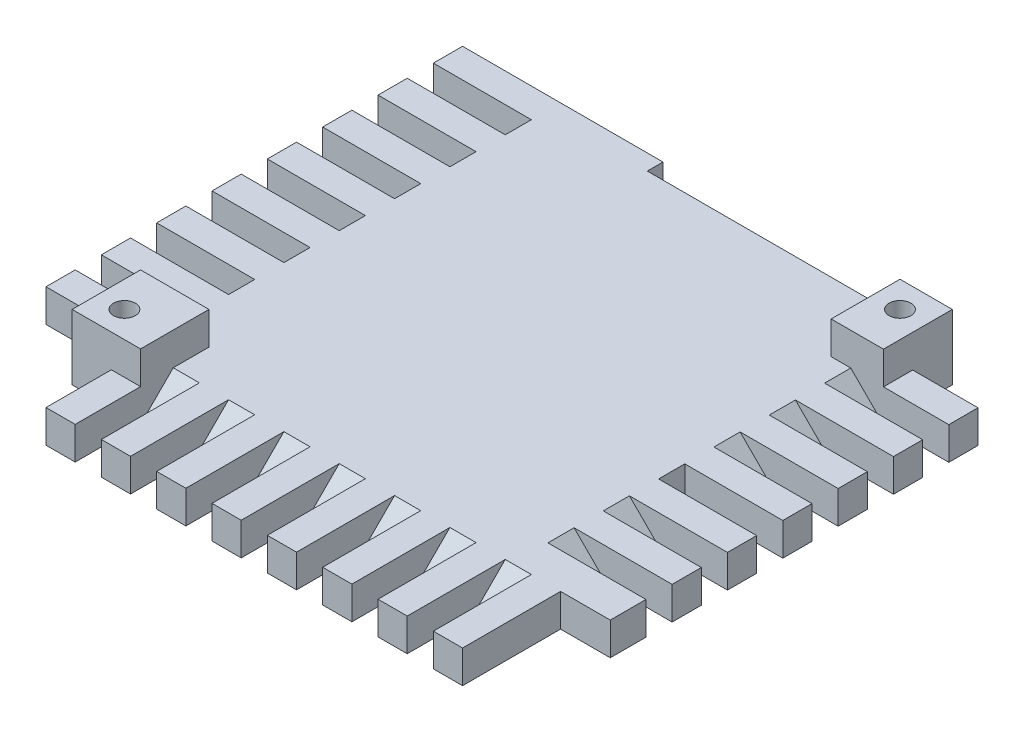
SolidWorks part; units mm, degrees
ref_plane "Front Plane" through (0, 0, 0) normal (0, 0, 1) x (1, 0, 0)
ref_plane "Top Plane" through (0, 0, 0) normal (0, 1, 0) x (1, 0, 0)
ref_plane "Right Plane" through (0, 0, 0) normal (1, 0, 0) x (0, 0, -1)
sketch "Base outline" plane through (0, 0, 0) normal (0, 1, 0) x (1, 0, 0)
  line L0 (3.74, 1.5) -> (3.74, 0) construction
  line L1 (6.2016, 20.2) -> (20.2, 20.2)
  line L4 (20.2, 20.2) -> (20.2, 18.38)
  line L6 (3.14, 0) -> (3.14, 1.5)
  line L7 (3.14, 1.5) -> (4.34, 1.5)
  line L8 (4.34, 0) -> (4.34, 1.5)
  line L10 (5.68, 0) -> (5.68, 1.5)
  line L11 (5.68, 1.5) -> (6.88, 1.5)
  line L12 (6.88, 0) -> (6.88, 1.5)
  line L13 (8.22, 0) -> (8.22, 1.5)
  line L14 (8.22, 1.5) -> (9.42, 1.5)
  line L15 (9.42, 0) -> (9.42, 1.5)
  line L16 (10.76, 0) -> (10.76, 1.5)
  line L17 (10.76, 1.5) -> (11.96, 1.5)
  line L18 (11.96, 0) -> (11.96, 1.5)
  line L19 (13.3, 0) -> (13.3, 1.5)
  line L20 (13.3, 1.5) -> (14.5, 1.5)
  line L21 (14.5, 0) -> (14.5, 1.5)
  line L22 (15.84, 0) -> (15.84, 1.5)
  line L23 (15.84, 1.5) -> (17.04, 1.5)
  line L24 (17.04, 0) -> (17.04, 1.5)
  line L25 (18.38, 0) -> (18.38, 1.5)
  line L26 (18.38, 1.5) -> (19.58, 1.5)
  line L27 (19.58, 0) -> (19.58, 1.5)
  line L28 (3.14, 0) -> (4.34, 0) construction
  line L35 (8.22, 0) -> (8.22, -3)
  line L37 (4.34, 0) -> (4.34, -3)
  line L38 (4.34, -3) -> (5.68, -3)
  line L39 (5.68, 0) -> (5.68, -3)
  line L40 (6.88, -3) -> (8.22, -3)
  line L41 (6.88, 0) -> (6.88, -3)
  line L42 (10.76, 0) -> (10.76, -3)
  line L43 (9.42, -3) -> (10.76, -3)
  line L44 (9.42, 0) -> (9.42, -3)
  line L45 (13.3, 0) -> (13.3, -3)
  line L46 (11.96, -3) -> (13.3, -3)
  line L47 (11.96, 0) -> (11.96, -3)
  line L48 (15.84, 0) -> (15.84, -3)
  line L49 (14.5, -3) -> (15.84, -3)
  line L50 (14.5, 0) -> (14.5, -3)
  line L51 (18.38, 0) -> (18.38, -3)
  line L52 (17.04, -3) -> (18.38, -3)
  line L53 (17.04, 0) -> (17.04, -3)
  line L54 (5.68, 0) -> (6.88, 0) construction
  line L55 (1.5, 3.74) -> (0, 3.74) construction
  line L56 (0, 3.14) -> (1.5, 3.14)
  line L58 (0, 4.34) -> (1.5, 4.34)
  line L59 (1.5, 3.14) -> (1.5, 4.34)
  line L61 (0, 6.88) -> (1.5, 6.88)
  line L62 (1.5, 5.68) -> (1.5, 6.88)
  line L63 (0, 5.68) -> (1.5, 5.68)
  line L64 (0, 9.42) -> (1.5, 9.42)
  line L65 (1.5, 8.22) -> (1.5, 9.42)
  line L66 (0, 8.22) -> (1.5, 8.22)
  line L67 (0, 11.96) -> (1.5, 11.96)
  line L68 (1.5, 10.76) -> (1.5, 11.96)
  line L69 (0, 10.76) -> (1.5, 10.76)
  line L70 (0, 14.5) -> (1.5, 14.5)
  line L71 (1.5, 13.3) -> (1.5, 14.5)
  line L72 (0, 13.3) -> (1.5, 13.3)
  line L73 (0, 17.04) -> (1.5, 17.04)
  line L74 (1.5, 15.84) -> (1.5, 17.04)
  line L75 (0, 15.84) -> (1.5, 15.84)
  line L76 (0, 19.58) -> (1.5, 19.58)
  line L77 (1.5, 18.38) -> (1.5, 19.58)
  line L78 (0, 18.38) -> (1.5, 18.38)
  line L79 (0, 6.88) -> (-3, 6.88)
  line L86 (-3, 6.88) -> (-3, 8.22)
  line L87 (0, 4.34) -> (-3, 4.34)
  line L89 (0, 5.68) -> (-3, 5.68)
  line L90 (-3, 4.34) -> (-3, 5.68)
  line L91 (0, 8.22) -> (-3, 8.22)
  line L92 (0, 9.42) -> (-3, 9.42)
  line L93 (-3, 9.42) -> (-3, 10.76)
  line L94 (0, 10.76) -> (-3, 10.76)
  line L95 (0, 11.96) -> (-3, 11.96)
  line L96 (-3, 11.96) -> (-3, 13.3)
  line L97 (0, 13.3) -> (-3, 13.3)
  line L98 (0, 14.5) -> (-3, 14.5)
  line L99 (-3, 14.5) -> (-3, 15.84)
  line L100 (0, 15.84) -> (-3, 15.84)
  line L101 (0, 17.04) -> (-3, 17.04)
  line L102 (-3, 17.04) -> (-3, 18.38)
  line L103 (0, 18.38) -> (-3, 18.38)
  line L104 (0, 4.34) -> (0, 6.88) construction
  line L105 (18.7, 3.74) -> (20.2, 3.74) construction
  line L106 (20.2, 4.34) -> (18.7, 4.34)
  line L108 (20.2, 3.14) -> (18.7, 3.14)
  line L109 (18.7, 4.34) -> (18.7, 3.14)
  line L111 (20.2, 6.88) -> (18.7, 6.88)
  line L112 (18.7, 6.88) -> (18.7, 5.68)
  line L113 (20.2, 5.68) -> (18.7, 5.68)
  line L114 (20.2, 9.42) -> (18.7, 9.42)
  line L115 (18.7, 9.42) -> (18.7, 8.22)
  line L116 (20.2, 8.22) -> (18.7, 8.22)
  line L117 (20.2, 11.96) -> (18.7, 11.96)
  line L118 (18.7, 11.96) -> (18.7, 10.76)
  line L119 (20.2, 10.76) -> (18.7, 10.76)
  line L120 (20.2, 14.5) -> (18.7, 14.5)
  line L121 (18.7, 14.5) -> (18.7, 13.3)
  line L122 (20.2, 13.3) -> (18.7, 13.3)
  line L123 (20.2, 17.04) -> (18.7, 17.04)
  line L124 (18.7, 17.04) -> (18.7, 15.84)
  line L125 (20.2, 15.84) -> (18.7, 15.84)
  line L129 (20.2, 8.22) -> (23.2, 8.22)
  line L135 (23.2, 8.22) -> (23.2, 6.88)
  line L136 (20.2, 5.68) -> (23.2, 5.68)
  line L138 (20.2, 4.34) -> (23.2, 4.34)
  line L139 (23.2, 5.68) -> (23.2, 4.34)
  line L140 (20.2, 6.88) -> (23.2, 6.88)
  line L141 (20.2, 10.76) -> (23.2, 10.76)
  line L142 (23.2, 10.76) -> (23.2, 9.42)
  line L143 (20.2, 9.42) -> (23.2, 9.42)
  line L144 (20.2, 13.3) -> (23.2, 13.3)
  line L145 (23.2, 13.3) -> (23.2, 11.96)
  line L146 (20.2, 11.96) -> (23.2, 11.96)
  line L147 (20.2, 15.84) -> (23.2, 15.84)
  line L148 (23.2, 15.84) -> (23.2, 14.5)
  line L149 (20.2, 14.5) -> (23.2, 14.5)
  line L150 (19.58, 0) -> (19.58, -3)
  line L151 (20.2, 3.14) -> (23.2, 3.14)
  line L153 (20.2, 5.68) -> (20.2, 6.88) construction
  line L155 (23.2, 3.14) -> (23.2, 1.5)
  line L156 (19.58, -3) -> (20.92, -3)
  line L158 (19.58, 0) -> (20.2, 0) construction
  line L159 (20.2, 0) -> (20.2, 3.14) construction
  line L160 (0, 3.14) -> (-3, 3.14)
  line L163 (23.2, 1.5) -> (20.92, 1.5)
  line L164 (20.92, -3) -> (20.92, 1.5)
  line L165 (-3, 3.14) -> (-3, 1.8)
  line L166 (1.8, -3) -> (3.14, -3)
  line L167 (3.14, -3) -> (3.14, 0)
  line L168 (0, 3.14) -> (0, 0) construction
  line L169 (0, 0) -> (3.14, 0) construction
  line L170 (0, 19.58) -> (-3, 19.58)
  line L171 (-3, 1.8) -> (0, 1.8)
  line L174 (0, 1.8) -> (0, 0)
  line L177 (0, 0) -> (1.8, 0)
  line L178 (1.8, -3) -> (1.8, 0)
  line L179 (-3, 19.58) -> (-3, 20.92)
  line L180 (-3, 20.92) -> (6.2016, 20.92)
  line L181 (6.2016, 20.92) -> (6.2016, 20.2)
  line L183 (20.2, 17.04) -> (23.2, 17.04)
  line L185 (20.2, 18.38) -> (23.2, 18.38)
  line L186 (23.2, 17.04) -> (23.2, 18.38)
  line L187 (20.2, 18.38) -> (18.7, 18.38) [skipped]
  line L188 (20.2, 19.58) -> (18.7, 19.58) [skipped]
  line L189 (18.7, 19.4) -> (18.7, 18.6) [skipped]
  circle A0 centre (1.2, 1.2) radius 0.5
  circle A1 centre (19, 19) radius 0.5
  dimension "D5" = 1
  dimension "D6" = 1
  dimension "D3" = 1.2
  dimension "D4" = 1.2
  dimension "D7" = 1.2
  dimension "D8" = 1.2
  dimension "D9" = 3.74
  dimension "D10" = 1.5
  dimension "D11" = 1.2
  dimension "D13" = 6
  dimension "D14" = 3
  dimension "D15" = 2.54
  dimension "D16" = 3.74
  dimension "D17" = 7
  dimension "D18" = 6
  dimension "D19" = 2.54
  dimension "D21" = 5
  dimension "D22" = 2.54
  dimension "D23" = 20.2
  dimension "D24" = 20.2
  dimension "D25" = 4.7016
  dimension "D12" = 7
  dimension "D20" = 7
extrude "Boss-Extrude1" add sketch "Base outline" along normal blind 1.5 contours L183 L186 L185 L4 L1 L181 L180 L179 L170 L76 L77 L78 L103 L102 L101 L73 L74 L75 L100 L99 L98 L70 L71 L72 L97 L96 L95 L67 L68 L69 L94 L93 L92 L64 L65 L66 L91 L86 L79 L61 L62 L63 L89 L90 L87 L58 L59 L56 L160 L165 L171 region at (10.0687, 0, -9.6701)
draft "Draft2" type of draft neutral plane draft angle 45 faces to draft 19 face at (1.5, 0.75, -18.98) face at (1.5, 0.75, -16.44) face at (1.5, 0.75, -13.9) face at (1.5, 0.75, -11.36) face at (1.5, 0.75, -8.82) face at (1.5, 0.75, -6.28) face at (1.5, 0.75, -3.74) face at (18.7, 0.75, -16.44) face at (18.7, 0.75, -13.9) face at (18.7, 0.75, -11.36) face at (18.7, 0.75, -6.28) face at (18.7, 0.75, -3.74) face at (18.98, 0.75, -1.5) face at (16.44, 0.75, -1.5) face at (13.9, 0.75, -1.5) face at (11.36, 0.75, -1.5) face at (8.82, 0.75, -1.5) face at (6.28, 0.75, -1.5) face at (3.74, 0.75, -1.5) neutral plane through (0, 1.5, 0) neutral plane normal (0, 1, 0) parameters "D1"=45
sketch "Spacer outline" plane through (0, 1.5, 0) normal (0, 1, 0) x (1, 0, 0)
  line L0 (0, 1.8) -> (0, 3.14)
  line L1 (-3, 3.14) -> (1.5, 3.14) construction
  line L2 (0, 3.14) -> (1.5, 3.14)
  line L3 (1.5, 3.14) -> (3.14, 3.14)
  line L4 (3.14, 3.14) -> (3.14, 1.5)
  line L5 (1.8, 0) -> (3.14, 0)
  line L6 (3.14, -3) -> (3.14, 1.5) construction
  line L7 (18.7, 17.04) -> (17.8, 17.04)
  line L8 (17.8, 17.04) -> (17.8, 20.2)
  line L9 (6.2016, 20.2) -> (20.2, 20.2) construction
  line L10 (20.2, 20.2) -> (20.2, 18.38) construction
  line L11 (20.2, 18.38) -> (20.2, 17.04)
  line L12 (18.7, 17.04) -> (23.2, 17.04) construction
  line L13 (0, 1.8) -> (0, 0)
  line L14 (0, 0) -> (1.8, 0)
  line L15 (3.14, 0) -> (3.14, 1.5)
  line L16 (20.2, 17.04) -> (18.7, 17.04)
  line L17 (17.8, 20.2) -> (20.2, 20.2)
  line L18 (20.2, 20.2) -> (20.2, 18.38)
  dimension "D1" = 2.4
extrude "Boss-Extrude2" add sketch "Spacer outline" along normal blind 1.5
extrude "Cut-Extrude1" cut sketch "Sketch1<3>" along normal blind 5.5 contours A0 | A1
sketch "Sketch1<3>" plane through (0, 0, 0) normal (0, 1, 0) x (1, 0, 0) same geometry as "Base outline"
sketch "PCB outline" plane through (0, 3, 0) normal (0, 1, 0) x (1, 0, 0)
  line L3 (3.74, 1.2) -> (6.28, 1.2) construction
  line L4 (0, 0) -> (20.2, 0) construction
  line L5 (0, 0) -> (0, 20.2) construction
  line L6 (0, 20.2) -> (20.2, 20.2) construction
  line L7 (20.2, 0) -> (20.2, 20.2) construction
  line L8 (18.98, 1.2) -> (18.98, 3.74) construction
  line L9 (1.2, 3.74) -> (1.2, 6.28) construction
  circle A0 centre (3.74, 1.2) radius 0.6 construction
  circle A1 centre (6.28, 1.2) radius 0.6 construction
  circle A2 centre (8.82, 1.2) radius 0.6 construction
  circle A3 centre (11.36, 1.2) radius 0.6 construction
  circle A4 centre (13.9, 1.2) radius 0.6 construction
  circle A5 centre (16.44, 1.2) radius 0.6 construction
  circle A6 centre (18.98, 1.2) radius 0.6 construction
  circle A7 centre (18.98, 3.74) radius 0.6 construction
  circle A8 centre (18.98, 6.28) radius 0.6 construction
  circle A9 centre (18.98, 8.82) radius 0.6 construction
  circle A10 centre (18.98, 11.36) radius 0.6 construction
  circle A11 centre (18.98, 13.9) radius 0.6 construction
  circle A12 centre (18.98, 16.44) radius 0.6 construction
  circle A13 centre (1.2, 3.74) radius 0.5 construction
  circle A14 centre (1.2, 6.28) radius 0.5 construction
  circle A15 centre (1.2, 8.82) radius 0.5 construction
  circle A16 centre (1.2, 11.36) radius 0.5 construction
  circle A17 centre (1.2, 13.9) radius 0.5 construction
  circle A18 centre (1.2, 16.44) radius 0.5 construction
  circle A19 centre (1.2, 18.98) radius 0.5 construction
  dimension "D1" = 1.2
  dimension "D8" = 1
  dimension "D2" = 1.2
  dimension "D3" = 3.74
  dimension "D5" = 2.54
  dimension "D7" = 2.54
  dimension "D9" = 1.2
  dimension "D10" = 3.74
  dimension "D12" = 2.54
  dimension "D4" = 7
  dimension "D6" = 7
  dimension "D11" = 7
sketch "Sketch3" plane through (0, 1.5, 0) normal (0, 1, 0) x (1, 0, 0)
  line L0 (3.74, 1.5) -> (3.74, 0) construction
  line L1 (6.2016, 20.2) -> (20.2, 20.2)
  line L4 (20.2, 20.2) -> (20.2, 18.38)
  line L6 (3.14, 0) -> (3.14, 1.5)
  line L7 (3.14, 1.5) -> (4.34, 1.5)
  line L8 (4.34, 0) -> (4.34, 1.5)
  line L10 (5.68, 0) -> (5.68, 1.5)
  line L11 (5.68, 1.5) -> (6.88, 1.5)
  line L12 (6.88, 0) -> (6.88, 1.5)
  line L13 (8.22, 0) -> (8.22, 1.5)
  line L14 (8.22, 1.5) -> (9.42, 1.5)
  line L15 (9.42, 0) -> (9.42, 1.5)
  line L16 (10.76, 0) -> (10.76, 1.5)
  line L17 (10.76, 1.5) -> (11.96, 1.5)
  line L18 (11.96, 0) -> (11.96, 1.5)
  line L19 (13.3, 0) -> (13.3, 1.5)
  line L20 (13.3, 1.5) -> (14.5, 1.5)
  line L21 (14.5, 0) -> (14.5, 1.5)
  line L22 (15.84, 0) -> (15.84, 1.5)
  line L23 (15.84, 1.5) -> (17.04, 1.5)
  line L24 (17.04, 0) -> (17.04, 1.5)
  line L25 (18.38, 0) -> (18.38, 1.5)
  line L26 (18.38, 1.5) -> (19.58, 1.5)
  line L27 (19.58, 0) -> (19.58, 1.5)
  line L28 (3.14, 0) -> (4.34, 0) construction
  line L35 (8.22, 0) -> (8.22, -3)
  line L37 (4.34, 0) -> (4.34, -3)
  line L38 (4.34, -3) -> (5.68, -3)
  line L39 (5.68, 0) -> (5.68, -3)
  line L40 (6.88, -3) -> (8.22, -3)
  line L41 (6.88, 0) -> (6.88, -3)
  line L42 (10.76, 0) -> (10.76, -3)
  line L43 (9.42, -3) -> (10.76, -3)
  line L44 (9.42, 0) -> (9.42, -3)
  line L45 (13.3, 0) -> (13.3, -3)
  line L46 (11.96, -3) -> (13.3, -3)
  line L47 (11.96, 0) -> (11.96, -3)
  line L48 (15.84, 0) -> (15.84, -3)
  line L49 (14.5, -3) -> (15.84, -3)
  line L50 (14.5, 0) -> (14.5, -3)
  line L51 (18.38, 0) -> (18.38, -3)
  line L52 (17.04, -3) -> (18.38, -3)
  line L53 (17.04, 0) -> (17.04, -3)
  line L54 (5.68, 0) -> (6.88, 0) construction
  line L55 (1.5, 3.74) -> (0, 3.74) construction
  line L56 (0, 3.14) -> (1.5, 3.14)
  line L58 (0, 4.34) -> (1.5, 4.34)
  line L59 (1.5, 3.14) -> (1.5, 4.34)
  line L61 (0, 6.88) -> (1.5, 6.88)
  line L62 (1.5, 5.68) -> (1.5, 6.88)
  line L63 (0, 5.68) -> (1.5, 5.68)
  line L64 (0, 9.42) -> (1.5, 9.42)
  line L65 (1.5, 8.22) -> (1.5, 9.42)
  line L66 (0, 8.22) -> (1.5, 8.22)
  line L67 (0, 11.96) -> (1.5, 11.96)
  line L68 (1.5, 10.76) -> (1.5, 11.96)
  line L69 (0, 10.76) -> (1.5, 10.76)
  line L70 (0, 14.5) -> (1.5, 14.5)
  line L71 (1.5, 13.3) -> (1.5, 14.5)
  line L72 (0, 13.3) -> (1.5, 13.3)
  line L73 (0, 17.04) -> (1.5, 17.04)
  line L74 (1.5, 15.84) -> (1.5, 17.04)
  line L75 (0, 15.84) -> (1.5, 15.84)
  line L76 (0, 19.58) -> (1.5, 19.58)
  line L77 (1.5, 18.38) -> (1.5, 19.58)
  line L78 (0, 18.38) -> (1.5, 18.38)
  line L79 (0, 6.88) -> (-3, 6.88)
  line L86 (-3, 6.88) -> (-3, 8.22)
  line L87 (0, 4.34) -> (-3, 4.34)
  line L89 (0, 5.68) -> (-3, 5.68)
  line L90 (-3, 4.34) -> (-3, 5.68)
  line L91 (0, 8.22) -> (-3, 8.22)
  line L92 (0, 9.42) -> (-3, 9.42)
  line L93 (-3, 9.42) -> (-3, 10.76)
  line L94 (0, 10.76) -> (-3, 10.76)
  line L95 (0, 11.96) -> (-3, 11.96)
  line L96 (-3, 11.96) -> (-3, 13.3)
  line L97 (0, 13.3) -> (-3, 13.3)
  line L98 (0, 14.5) -> (-3, 14.5)
  line L99 (-3, 14.5) -> (-3, 15.84)
  line L100 (0, 15.84) -> (-3, 15.84)
  line L101 (0, 17.04) -> (-3, 17.04)
  line L102 (-3, 17.04) -> (-3, 18.38)
  line L103 (0, 18.38) -> (-3, 18.38)
  line L104 (0, 4.34) -> (0, 6.88) construction
  line L105 (18.7, 3.74) -> (20.2, 3.74) construction
  line L106 (20.2, 4.34) -> (18.7, 4.34)
  line L108 (20.2, 3.14) -> (18.7, 3.14)
  line L109 (18.7, 4.34) -> (18.7, 3.14)
  line L111 (20.2, 6.88) -> (18.7, 6.88)
  line L112 (18.7, 6.88) -> (18.7, 5.68)
  line L113 (20.2, 5.68) -> (18.7, 5.68)
  line L114 (20.2, 9.42) -> (18.7, 9.42)
  line L115 (18.7, 9.42) -> (18.7, 8.22)
  line L116 (20.2, 8.22) -> (18.7, 8.22)
  line L117 (20.2, 11.96) -> (18.7, 11.96)
  line L118 (18.7, 11.96) -> (18.7, 10.76)
  line L119 (20.2, 10.76) -> (18.7, 10.76)
  line L120 (20.2, 14.5) -> (18.7, 14.5)
  line L121 (18.7, 14.5) -> (18.7, 13.3)
  line L122 (20.2, 13.3) -> (18.7, 13.3)
  line L123 (20.2, 17.04) -> (18.7, 17.04)
  line L124 (18.7, 17.04) -> (18.7, 15.84)
  line L125 (20.2, 15.84) -> (18.7, 15.84)
  line L129 (20.2, 8.22) -> (23.2, 8.22)
  line L135 (23.2, 8.22) -> (23.2, 6.88)
  line L136 (20.2, 5.68) -> (23.2, 5.68)
  line L138 (20.2, 4.34) -> (23.2, 4.34)
  line L139 (23.2, 5.68) -> (23.2, 4.34)
  line L140 (20.2, 6.88) -> (23.2, 6.88)
  line L141 (20.2, 10.76) -> (23.2, 10.76)
  line L142 (23.2, 10.76) -> (23.2, 9.42)
  line L143 (20.2, 9.42) -> (23.2, 9.42)
  line L144 (20.2, 13.3) -> (23.2, 13.3)
  line L145 (23.2, 13.3) -> (23.2, 11.96)
  line L146 (20.2, 11.96) -> (23.2, 11.96)
  line L147 (20.2, 15.84) -> (23.2, 15.84)
  line L148 (23.2, 15.84) -> (23.2, 14.5)
  line L149 (20.2, 14.5) -> (23.2, 14.5)
  line L150 (19.58, 0) -> (19.58, -3)
  line L151 (20.2, 3.14) -> (23.2, 3.14)
  line L153 (20.2, 5.68) -> (20.2, 6.88) construction
  line L155 (23.2, 3.14) -> (23.2, 1.5)
  line L156 (19.58, -3) -> (20.92, -3)
  line L158 (19.58, 0) -> (20.2, 0) construction
  line L159 (20.2, 0) -> (20.2, 3.14) construction
  line L160 (0, 3.14) -> (-3, 3.14)
  line L163 (23.2, 1.5) -> (20.92, 1.5)
  line L164 (20.92, -3) -> (20.92, 1.5)
  line L165 (-3, 3.14) -> (-3, 1.8)
  line L166 (1.8, -3) -> (3.14, -3)
  line L167 (3.14, -3) -> (3.14, 0)
  line L168 (0, 3.14) -> (0, 0) construction
  line L169 (0, 0) -> (3.14, 0) construction
  line L170 (0, 19.58) -> (-3, 19.58)
  line L171 (-3, 1.8) -> (0, 1.8)
  line L174 (0, 1.8) -> (0, 0)
  line L177 (0, 0) -> (1.8, 0)
  line L178 (1.8, -3) -> (1.8, 0)
  line L179 (-3, 19.58) -> (-3, 20.92)
  line L180 (-3, 20.92) -> (6.2016, 20.92)
  line L181 (6.2016, 20.92) -> (6.2016, 20.2)
  line L183 (20.2, 17.04) -> (23.2, 17.04)
  line L185 (20.2, 18.38) -> (23.2, 18.38)
  line L186 (23.2, 17.04) -> (23.2, 18.38)
  line L187 (20.2, 18.38) -> (18.7, 18.38)
  line L188 (20.2, 19.58) -> (18.7, 19.58)
  line L189 (18.7, 22.9851) -> (18.7, 22.1851)
  circle A0 centre (1.2, 1.2) radius 0.5
  circle A1 centre (19, 19) radius 0.5
  dimension "D5" = 1
  dimension "D6" = 1
  dimension "D3" = 1.2
  dimension "D4" = 1.2
  dimension "D7" = 1.2
  dimension "D8" = 1.2
  dimension "D9" = 3.74
  dimension "D10" = 1.5
  dimension "D11" = 1.2
  dimension "D13" = 6
  dimension "D14" = 3
  dimension "D15" = 2.54
  dimension "D16" = 3.74
  dimension "D17" = 7
  dimension "D18" = 6
  dimension "D19" = 2.54
  dimension "D21" = 5
  dimension "D22" = 2.54
  dimension "D23" = 20.2
  dimension "D24" = 20.2
  dimension "D25" = 4.7016
  dimension "D12" = 7
  dimension "D20" = 7
